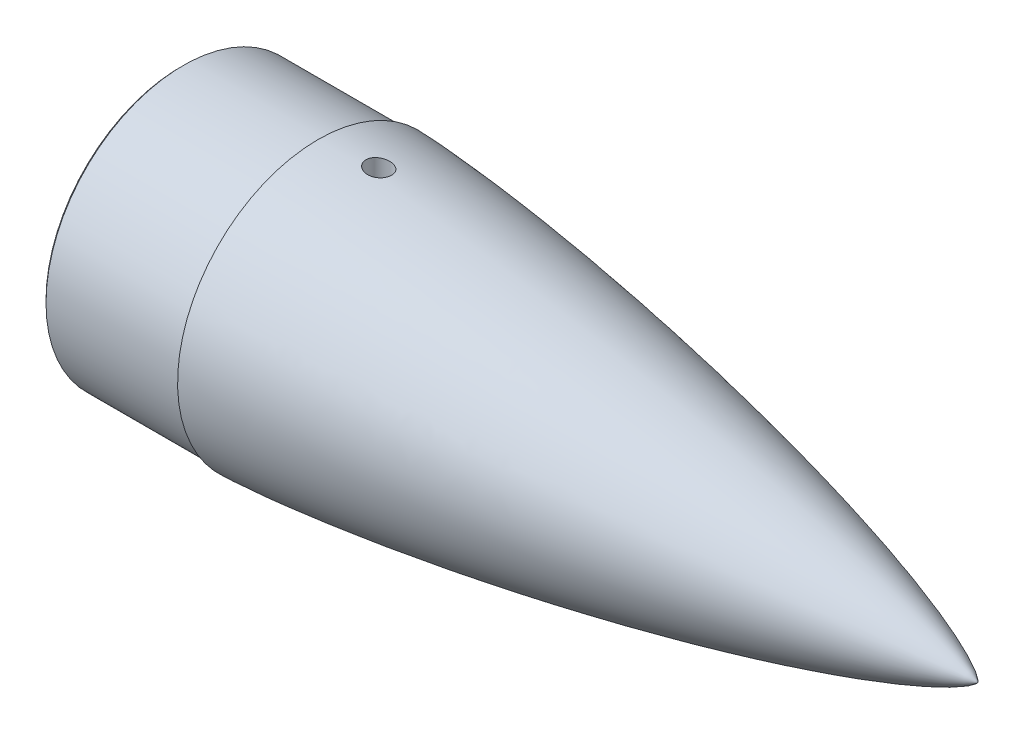
SolidWorks part; units mm, degrees
material "Plain Carbon Steel"
ref_plane "Front Plane" through (0, 0, 0) normal (0, 0, 1) x (1, 0, 0)
ref_plane "Top Plane" through (0, 0, 0) normal (0, 1, 0) x (1, 0, 0)
ref_plane "Right Plane" through (0, 0, 0) normal (1, 0, 0) x (0, 0, -1)
ref_axis "Axis1" through (46.9179, 0, 0) along (-1, 0, 0)
sketch "Sketch10" plane through (0, 0, 0) normal (0, 0, 1) x (1, 0, 0)
  line L1 (-1.0327, 0) -> (486.9547, 0) construction
  line L2 (11.1125, 81.9998) -> (11.1125, 67.4998)
  line L3 (11.1125, 81.9998) -> (-84.6045, 81.9998)
  line L4 (408.9673, 0) -> (368.9673, 0)
  line L5 (-84.6045, 81.9998) -> (-84.6045, 84.9998)
  line L6 (-84.6045, 84.9998) -> (0.3953, 84.9998)
  line L7 (0.3953, 84.9998) -> (0.3953, 86.9998)
  line L8 (11.1125, 67.4998) -> (129.3045, 67.4998)
  spline S0 degree 4 poles (408.9673, 0) (408.9649, 0.0135) (408.958, 0.0399) (408.9365, 0.0905) (408.8922, 0.1741) (408.8263, 0.2756) (408.7217, 0.4158) (408.5611, 0.6051) (408.3056, 0.8724) (407.8697, 1.2753) (407.121, 1.8851) (405.8038, 2.8259) (403.4624, 4.2872) (399.3253, 6.5318) (392.4811, 9.7589) (380.6621, 14.628) (363.6372, 20.7117) (342.2152, 27.4765) (317.4285, 34.4976) (291.8793, 41.1048) (266.2105, 47.229) (240.4455, 52.9334) (214.5989, 58.2554) (188.6809, 63.2176) (165.9462, 67.2533) (146.422, 70.4938) (130.1279, 73.0449) (117.0786, 74.9942) (104.0155, 76.8485) (92.5733, 78.3845) (82.7571, 79.6356) (74.5713, 80.6322) (68.0193, 81.4008) (61.4637, 82.1394) (54.9047, 82.8464) (48.3422, 83.5199) (41.7761, 84.1578) (36.0275, 84.6822) (31.0979, 85.1052) (26.9883, 85.4387) (23.6997, 85.6932) (20.0858, 85.9584) (16.7199, 86.189) (13.6021, 86.387) (10.7327, 86.5546) (8.4366, 86.6787) (6.14, 86.7922) (4.1299, 86.8793) (2.4065, 86.9446) (1.2573, 86.979) (0.6827, 86.9949) (0.3953, 86.9998) knots 0 0 0 0 0 0.00013 0.00026 0.00052 0.0009 0.00128 0.001925 0.002882 0.004418 0.006927 0.011111 0.018279 0.030673 0.051704 0.083102 0.139909 0.202703 0.265496 0.32829 0.391083 0.453877 0.516671 0.579464 0.642258 0.673655 0.705051 0.736448 0.767845 0.799242 0.81494 0.830639 0.846337 0.862036 0.877734 0.893432 0.909131 0.924829 0.932678 0.940527 0.948377 0.956226 0.967169 0.972641 0.978113 0.983585 0.989056 0.994528 0.997264 1 1 1 1 1 construction
  spline S1 degree 4 poles (408.9673, 0) (408.9649, 0.0135) (408.958, 0.0399) (408.9365, 0.0905) (408.8922, 0.1741) (408.8263, 0.2756) (408.7217, 0.4158) (408.5611, 0.6051) (408.3056, 0.8724) (407.8697, 1.2753) (407.121, 1.8851) (405.8038, 2.8259) (403.4624, 4.2872) (399.3253, 6.5318) (392.4811, 9.7589) (380.6621, 14.628) (363.6372, 20.7117) (342.2152, 27.4765) (317.4285, 34.4976) (291.8793, 41.1048) (266.2105, 47.229) (240.4455, 52.9334) (214.5989, 58.2554) (188.6809, 63.2176) (165.9462, 67.2533) (146.422, 70.4938) (130.1279, 73.0449) (117.0786, 74.9942) (104.0155, 76.8485) (92.5733, 78.3845) (82.7571, 79.6356) (74.5713, 80.6322) (68.0193, 81.4008) (61.4637, 82.1394) (54.9047, 82.8464) (48.3422, 83.5199) (41.7761, 84.1578) (36.0275, 84.6822) (31.0979, 85.1052) (26.9883, 85.4387) (23.6997, 85.6932) (20.0858, 85.9584) (16.7199, 86.189) (13.6021, 86.387) (10.7327, 86.5546) (8.4366, 86.6787) (6.14, 86.7922) (4.1299, 86.8793) (2.4065, 86.9446) (1.2573, 86.979) (0.6827, 86.9949) (0.3953, 86.9998) knots 0 0 0 0 0 0.00013 0.00026 0.00052 0.0009 0.00128 0.001925 0.002882 0.004418 0.006927 0.011111 0.018279 0.030673 0.051704 0.083102 0.139909 0.202703 0.265496 0.32829 0.391083 0.453877 0.516671 0.579464 0.642258 0.673655 0.705051 0.736448 0.767845 0.799242 0.81494 0.830639 0.846337 0.862036 0.877734 0.893432 0.909131 0.924829 0.932678 0.940527 0.948377 0.956226 0.967169 0.972641 0.978113 0.983585 0.989056 0.994528 0.997264 1 1 1 1 1
  spline S2 degree 4 poles (368.9673, 0) (368.9653, 0.0123) (368.9594, 0.0365) (368.9406, 0.083) (368.9023, 0.1587) (368.8455, 0.2503) (368.7557, 0.3766) (368.6167, 0.5484) (368.3929, 0.7936) (368.0087, 1.1649) (367.3447, 1.7299) (366.1761, 2.6016) (364.0928, 3.96) (360.426, 6.0407) (354.4022, 9.0183) (344.043, 13.5077) (329.152, 19.1285) (310.4252, 25.3986) (288.7413, 31.9337) (266.3785, 38.1061) (243.9014, 43.8469) (221.332, 49.212) (198.684, 54.2345) (175.9669, 58.9343) (156.0346, 62.7717) (138.9133, 65.8645) (124.6221, 68.3077) (113.1754, 70.1797) (101.7151, 71.9664) (91.6754, 73.4517) (83.0615, 74.6659) (75.8775, 75.6363) (70.1269, 76.3867) (64.3728, 77.1101) (58.6152, 77.8049) (52.854, 78.4695) (47.0892, 79.1019) (42.0417, 79.6247) (37.7129, 80.0488) (34.1039, 80.385) (31.2157, 80.6428) (28.0648, 80.911) (24.6507, 81.1843) (21.4654, 81.4195) (18.5093, 81.6177) (16.0448, 81.767) (14.3191, 81.8612) (12.8395, 81.9336) (11.8527, 81.9739) (11.3593, 81.993) (11.1125, 81.9998) knots 0 0 0 0 0 0.000135 0.00027 0.00054 0.00092 0.001299 0.001947 0.002931 0.004512 0.007081 0.01138 0.018708 0.031424 0.052705 0.084103 0.14091 0.203703 0.266497 0.329291 0.392084 0.454878 0.517672 0.580465 0.643259 0.674656 0.706052 0.737449 0.768846 0.800243 0.815941 0.831639 0.847338 0.863036 0.878735 0.894433 0.910132 0.92583 0.933679 0.941528 0.949378 0.957227 0.96792 0.978613 0.98396 0.989307 0.994653 0.997327 1 1 1 1 1 construction
  spline S3 degree 4 poles (368.9673, 0) (368.9653, 0.0123) (368.9594, 0.0365) (368.9406, 0.083) (368.9023, 0.1587) (368.8455, 0.2503) (368.7557, 0.3766) (368.6167, 0.5484) (368.3929, 0.7936) (368.0087, 1.1649) (367.3447, 1.7299) (366.1761, 2.6016) (364.0928, 3.96) (360.426, 6.0407) (354.4022, 9.0183) (344.043, 13.5077) (329.152, 19.1285) (310.4252, 25.3986) (288.7413, 31.9337) (266.3785, 38.1061) (243.9014, 43.8469) (221.332, 49.212) (198.684, 54.2345) (175.9669, 58.9343) (156.0346, 62.7717) (141.5091, 65.3956) (132.6794, 66.9245) (129.5628, 67.4559) (129.3045, 67.4998) knots 0 0 0 0 0 0.000135 0.00027 0.00054 0.00092 0.001299 0.001947 0.002931 0.004512 0.007081 0.01138 0.018708 0.031424 0.052705 0.084103 0.14091 0.203703 0.266497 0.329291 0.392084 0.454878 0.517672 0.580465 0.643259 0.674656 0.677492 0.677492 0.677492 0.677492 0.677492
  dimension "D1" = 86.9998
  dimension "D2" = 3
  dimension "D3" = 410
  dimension "D4" = 84.9998
  dimension "D5" = 370
  dimension "D6" = 84.9998
  dimension "D7" = 19.5
  dimension "D8" = 118.192
revolve "Revolve1" add sketch "Sketch10" angle 360 about axis through (46.9179, 0, 0) along (-1, 0, 0)
chamfer "Chamfer1" distance 1.5 angle 45 1 edges at (-84.6045, 0, -84.9998)
ref_plane "Plane2" through (11.1125, 0, 0) normal (-1, 0, 0) x (0, 0, 1)
sketch "Sketch12" plane through (11.1125, 0, 0) normal (-1, 0, 0) x (0, 0, 1)
  line L0 (-81.9998, 0) -> (-67.4998, 0)
  circle A2 centre (0, 0) radius 81.9998 construction
  circle A3 centre (0, 0) radius 67.4998 construction
  circle A4 centre (-74.7498, 0) radius 4
  circle A5 centre (-37.3749, 64.7353) radius 4
  circle A6 centre (37.3749, 64.7353) radius 4
  circle A7 centre (74.7498, 0) radius 4
  circle A8 centre (37.3749, -64.7353) radius 4
  circle A9 centre (-37.3749, -64.7353) radius 4
  point P17 (-50.2998, -44.6412)
  point P25 (0, 0)
  dimension "D1" = 6
hole_wizard "Tapped Hole for M4x0.7 Helicoil1" positions "Sketch17" profile "Sketch18" tap size "M4x0.7" standard "Helicoil® Metric"
sketch "Sketch17" plane through (11.1125, 0, 0) normal (-1, 0, 0) x (0, 0, 1)
  point P0 (-37.3749, 64.7353)
sketch "Sketch18" plane through (11.1125, 64.7353, -37.3749) normal (0, 1, 0) x (0, 0, 1)
  line L0 (0, 0) -> (0, 31.2618)
  line L1 (0, 31.2618) -> (2.1, 30)
  line L2 (2.1, 30) -> (2.1, 0)
  line L5 (2.1, 0) -> (0, 0)
  line L10 (0, 31.2618) -> (-2.1, 30) construction
  line L11 (0, -6.35) -> (0, 107.95) construction
  dimension "Tap Drill Dia." = 4.2
  dimension "Tap Drill Depth" = 30
  dimension "Drill Angle" = 118
cosmetic thread "Hole Thread3" parameters "D1"=4.7, "D2"=5.007
pattern_circular "CirPattern1" count 6 over 360 about axis through (11.1125, 0, 0) along (1, 0, 0) of "Tapped Hole for M4x0.7 Helicoil1"
ref_plane "Plane3" through (0, 60, 0) normal (0, 1, 0) x (1, 0, 0)
sketch "Sketch20" plane through (0, 60, 0) normal (0, 1, 0) x (1, 0, 0)
  line L0 (46.9179, 0) -> (-46.1272, 0) construction
  line L1 (24.7702, 25) -> (64.7702, 25)
  line L2 (24.7702, 25) -> (24.7702, -15)
  line L3 (24.7702, -15) -> (64.7702, -15)
  line L4 (64.7702, 25) -> (64.7702, -15)
  line L5 (24.7702, 25) -> (64.7702, -15) construction
  line L6 (24.7702, -15) -> (64.7702, 25) construction
  point P4 (44.7702, 5)
  dimension "D1" = 40
  dimension "D2" = 15
  dimension "D3" = 40
extrude "Cut-Extrude3" cut sketch "Sketch20" along normal blind 12
sketch "Sketch22" plane through (0, 60, 0) normal (0, 1, 0) x (1, 0, 0)
  circle A0 centre (32, 6) radius 7.5
  dimension "D1" = 15
extrude "Cut-Extrude4" cut sketch "Sketch22" along normal through all
